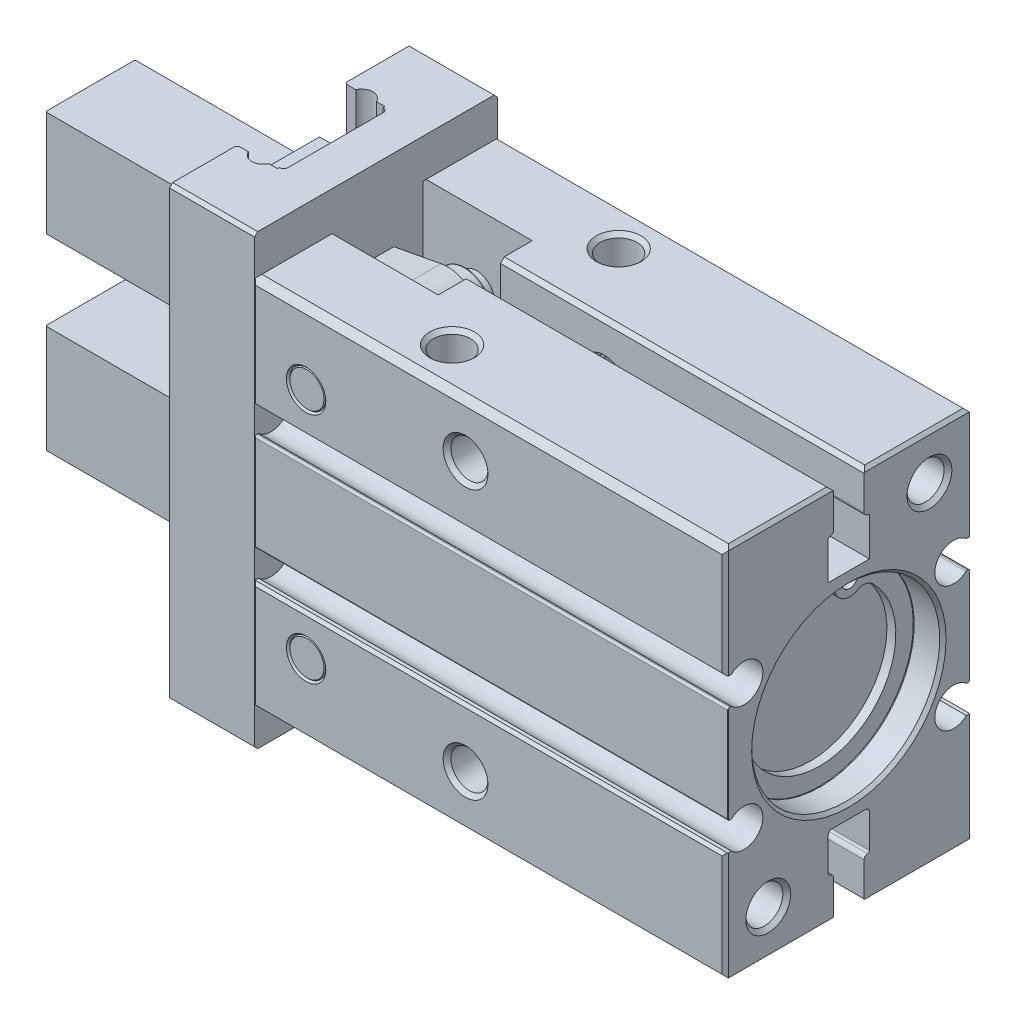
SolidWorks part; units mm, degrees
ref_plane "前视基准面" through (0, 0, 0) normal (0, 0, 1) x (1, 0, 0)
ref_plane "上视基准面" through (0, 0, 0) normal (0, 1, 0) x (1, 0, 0)
ref_plane "右视基准面" through (0, 0, 0) normal (1, 0, 0) x (0, 0, -1)
ref_plane "基准面1" through (0, 0, 0) normal (1, 0, 0) x (0, 0, -1)
sketch "草图1" plane through (0, 0, 0) normal (1, 0, 0) x (0, 0, -1)
  line L0 (-13.8, 20.2929) -> (-13.8, 8.85)
  line L1 (-13.8, 8.85) -> (-13.5, 8.55)
  line L2 (-13.5, 8.55) -> (-13.1169, 8.55)
  line L3 (-13.1925, 5.45) -> (-13.3, 5.45)
  line L4 (-13.5, 5.25) -> (-13.5, -5.25)
  line L5 (-13.3, -5.45) -> (-13.1925, -5.45)
  line L6 (-13.1169, -8.55) -> (-13.5, -8.55)
  line L7 (-13.5, -8.55) -> (-13.8, -8.85)
  line L8 (-13.8, -8.85) -> (-13.8, -20.2929)
  line L9 (-13.8, -20.2929) -> (-13.0929, -21)
  line L10 (-13.0929, -21) -> (-2.1243, -21)
  line L11 (-2.1243, -21) -> (-1.7, -20.5757)
  line L12 (-1.7, -20.5757) -> (-1.7, -16.8)
  line L13 (-2.3, -16.2) -> (-2.3, -12.4)
  line L14 (-1.9, -12) -> (1.9, -12)
  line L15 (2.3, -12.4) -> (2.3, -16.2)
  line L16 (1.7, -16.8) -> (1.7, -20.5757)
  line L17 (1.7, -20.5757) -> (2.1243, -21)
  line L18 (2.1243, -21) -> (13.0929, -21)
  line L19 (13.0929, -21) -> (13.8, -20.2929)
  line L20 (13.8, -20.2929) -> (13.8, -8.85)
  line L21 (13.8, -8.85) -> (13.5, -8.55)
  line L22 (13.5, -8.55) -> (13.1169, -8.55)
  line L23 (13.1925, -5.45) -> (13.3, -5.45)
  line L24 (13.5, -5.25) -> (13.5, 5.25)
  line L25 (13.3, 5.45) -> (13.1925, 5.45)
  line L26 (13.1169, 8.55) -> (13.5, 8.55)
  line L27 (13.5, 8.55) -> (13.8, 8.85)
  line L28 (13.8, 8.85) -> (13.8, 20.2929)
  line L29 (13.8, 20.2929) -> (13.0929, 21)
  line L30 (13.0929, 21) -> (2.1243, 21)
  line L31 (2.1243, 21) -> (1.7, 20.5757)
  line L32 (1.7, 20.5757) -> (1.7, 16.8)
  line L33 (2.3, 16.2) -> (2.3, 12)
  line L34 (2.3, 12) -> (-2.3, 12)
  line L35 (-2.3, 12) -> (-2.3, 16.2)
  line L36 (-1.7, 16.8) -> (-1.7, 20.5757)
  line L37 (-1.7, 20.5757) -> (-2.1243, 21)
  line L38 (-2.1243, 21) -> (-13.0929, 21)
  line L39 (-13.0929, 21) -> (-13.8, 20.2929)
  arc A0 (-13.1169, 8.55) -> (-13.0627, 5.4022) centre (-11.7, 7) cw
  arc A1 (-13.0627, 5.4022) -> (-13.1925, 5.45) centre (-13.1925, 5.25) ccw
  arc A2 (-13.3, 5.45) -> (-13.5, 5.25) centre (-13.3, 5.25) ccw
  arc A3 (-13.5, -5.25) -> (-13.3, -5.45) centre (-13.3, -5.25) ccw
  arc A4 (-13.1925, -5.45) -> (-13.0627, -5.4022) centre (-13.1925, -5.25) ccw
  arc A5 (-13.0627, -5.4022) -> (-13.1169, -8.55) centre (-11.7, -7) cw
  arc A6 (-1.7, -16.8) -> (-2.1, -16.4) centre (-2.1, -16.8) ccw
  arc A7 (-2.1, -16.4) -> (-2.3, -16.2) centre (-2.1, -16.2) cw
  arc A8 (-2.3, -12.4) -> (-1.9, -12) centre (-1.9, -12.4) cw
  arc A9 (1.9, -12) -> (2.3, -12.4) centre (1.9, -12.4) cw
  arc A10 (2.3, -16.2) -> (2.1, -16.4) centre (2.1, -16.2) cw
  arc A11 (2.1, -16.4) -> (1.7, -16.8) centre (2.1, -16.8) ccw
  arc A12 (13.1169, -8.55) -> (13.0627, -5.4022) centre (11.7, -7) cw
  arc A13 (13.0627, -5.4022) -> (13.1925, -5.45) centre (13.1925, -5.25) ccw
  arc A14 (13.3, -5.45) -> (13.5, -5.25) centre (13.3, -5.25) ccw
  arc A15 (13.5, 5.25) -> (13.3, 5.45) centre (13.3, 5.25) ccw
  arc A16 (13.1925, 5.45) -> (13.0627, 5.4022) centre (13.1925, 5.25) ccw
  arc A17 (13.0627, 5.4022) -> (13.1169, 8.55) centre (11.7, 7) cw
  arc A18 (1.7, 16.8) -> (2.1, 16.4) centre (2.1, 16.8) ccw
  arc A19 (2.1, 16.4) -> (2.3, 16.2) centre (2.1, 16.2) cw
  arc A20 (-2.3, 16.2) -> (-2.1, 16.4) centre (-2.1, 16.2) cw
  arc A21 (-2.1, 16.4) -> (-1.7, 16.8) centre (-2.1, 16.8) ccw
extrude "凸台-拉伸1" add sketch "草图1" against normal blind 52.8
ref_plane "基准面2" through (0, 0, 0) normal (0, 1, 0) x (1, 0, 0)
sketch "草图2" plane through (0, 0, 0) normal (0, 1, 0) x (1, 0, 0)
  line L0 (-52.8, 5.25) -> (-52.8, -5.25)
  line L1 (-52.8, -5.25) -> (-40.6, -5.25)
  line L2 (-40.6, -5.25) -> (-40.6, 5.25)
  line L3 (-40.6, 5.25) -> (-52.8, 5.25)
extrude "切除-拉伸1" cut sketch "草图2" against normal blind 21 and the other way blind 21
ref_plane "基准面3" through (-29, 0, 0) normal (1, 0, 0) x (0, 0, -1)
sketch "草图3" plane through (-29, 0, 0) normal (1, 0, 0) x (0, 0, -1)
  line L0 (-13.8, 15) -> (-13.8, 17.5)
  line L1 (-13.8, 17.5) -> (-13.367, 17.067)
  line L2 (-13.367, 17.067) -> (-3.8, 17.067)
  line L3 (-3.8, 17.067) -> (-3.8, 17.51)
  line L4 (-3.8, 17.51) -> (3.8, 17.51)
  line L5 (3.8, 17.51) -> (3.8, 17.067)
  line L6 (3.8, 17.067) -> (13.367, 17.067)
  line L7 (13.367, 17.067) -> (13.8, 17.5)
  line L8 (13.8, 17.5) -> (13.8, 15)
  line L9 (13.8, 15) -> (-13.8, 15)
  line L10 (13.8, 15) -> (-13.8, 15) construction
revolve "切除-旋转1" cut sketch "草图3" angle 360 about L10 reverse direction yes
ref_plane "基准面4" through (-29, 0, 0) normal (1, 0, 0) x (0, 0, -1)
sketch "草图4" plane through (-29, 0, 0) normal (1, 0, 0) x (0, 0, -1)
  line L0 (-13.8, -15) -> (-13.8, -12.5)
  line L1 (-13.8, -12.5) -> (-13.367, -12.933)
  line L2 (-13.367, -12.933) -> (-3.8, -12.933)
  line L3 (-3.8, -12.933) -> (-3.8, -12.49)
  line L4 (-3.8, -12.49) -> (3.8, -12.49)
  line L5 (3.8, -12.49) -> (3.8, -12.933)
  line L6 (3.8, -12.933) -> (13.367, -12.933)
  line L7 (13.367, -12.933) -> (13.8, -12.5)
  line L8 (13.8, -12.5) -> (13.8, -15)
  line L9 (13.8, -15) -> (-13.8, -15)
  line L10 (13.8, -15) -> (-13.8, -15) construction
revolve "切除-旋转2" cut sketch "草图4" angle 360 about L10 reverse direction yes
ref_plane "基准面5" through (0, 0, 0) normal (0, 1, 0) x (1, 0, 0)
sketch "草图5" plane through (0, 0, 0) normal (0, 1, 0) x (1, 0, 0)
  line L0 (-53.8, -14.8) -> (1, -14.8)
  line L1 (1, -14.8) -> (1, 14.8)
  line L2 (1, 14.8) -> (-53.8, 14.8)
  line L3 (-53.8, 14.8) -> (-53.8, -14.8)
  line L4 (-52.8, 13.4464) -> (-52.8, -13.4464)
  line L5 (-52.8, -13.4464) -> (-52.4464, -13.8)
  line L6 (-52.4464, -13.8) -> (-0.3536, -13.8)
  line L7 (-0.3536, -13.8) -> (0, -13.4464)
  line L8 (0, -13.4464) -> (0, 13.4464)
  line L9 (0, 13.4464) -> (-0.3536, 13.8)
  line L10 (-0.3536, 13.8) -> (-52.4464, 13.8)
  line L11 (-52.4464, 13.8) -> (-52.8, 13.4464)
extrude "切除-拉伸2" cut sketch "草图5" against normal blind 21 and the other way blind 21
ref_plane "基准面6" through (0, 0, 0) normal (0, 0, 1) x (1, 0, 0)
sketch "草图6" plane through (0, 0, 0) normal (0, 0, 1) x (1, 0, 0)
  line L0 (-53.8, 22) -> (-53.8, -22)
  line L1 (-53.8, -22) -> (1, -22)
  line L2 (1, -22) -> (1, 22)
  line L3 (1, 22) -> (-53.8, 22)
  line L4 (-52.8, -20.6464) -> (-52.4464, -21)
  line L5 (-52.4464, -21) -> (-0.3536, -21)
  line L6 (-0.3536, -21) -> (0, -20.6464)
  line L7 (0, -20.6464) -> (0, 20.6464)
  line L8 (0, 20.6464) -> (-0.3536, 21)
  line L9 (-0.3536, 21) -> (-52.4464, 21)
  line L10 (-52.4464, 21) -> (-52.8, 20.6464)
  line L11 (-52.8, 20.6464) -> (-52.8, -20.6464)
extrude "切除-拉伸3" cut sketch "草图6" against normal blind 13.8 and the other way blind 13.8
ref_plane "基准面7" through (-52.8, 0, 0) normal (1, 0, 0) x (0, 0, -1)
sketch "草图7" plane through (-52.8, 0, 0) normal (1, 0, 0) x (0, 0, -1)
  line L0 (-13.55, -24.6464) -> (-13.1964, -25)
  line L1 (-13.1964, -25) -> (13.1964, -25)
  line L2 (13.1964, -25) -> (13.55, -24.6464)
  line L3 (13.55, -24.6464) -> (13.55, 24.6464)
  line L4 (13.55, 24.6464) -> (13.1964, 25)
  line L5 (13.1964, 25) -> (-13.1964, 25)
  line L6 (-13.1964, 25) -> (-13.55, 24.6464)
  line L7 (-13.55, 24.6464) -> (-13.55, -24.6464)
extrude "凸台-拉伸2" add sketch "草图7" against normal blind 9.5
ref_plane "基准面8" through (0, 0, 0) normal (0, 1, 0) x (1, 0, 0)
sketch "草图8" plane through (0, 0, 0) normal (0, 1, 0) x (1, 0, 0)
  line L0 (-62.3, -6.2121) -> (-62.0879, -6)
  line L1 (-62.0879, -6) -> (-61.0456, -6)
  line L2 (-58.7544, -6) -> (-57.8, -6)
  line L3 (-57.8, -6) -> (-57.8, -5.8)
  line L4 (-57.3, -5.3) -> (-57.3, 5.3)
  line L5 (-57.8, 5.8) -> (-57.8, 6)
  line L6 (-57.8, 6) -> (-58.7544, 6)
  line L7 (-61.0456, 6) -> (-62.0879, 6)
  line L8 (-62.0879, 6) -> (-62.3, 6.2121)
  line L9 (-62.3, 6.2121) -> (-62.3, -6.2121)
  arc A0 (-61.0456, -6) -> (-58.7544, -6) centre (-59.9, -5.5) ccw
  arc A1 (-57.8, -5.8) -> (-57.3, -5.3) centre (-57.8, -5.3) ccw
  arc A2 (-57.3, 5.3) -> (-57.8, 5.8) centre (-57.8, 5.3) ccw
  arc A3 (-58.7544, 6) -> (-61.0456, 6) centre (-59.9, 5.5) ccw
extrude "切除-拉伸4" cut sketch "草图8" against normal blind 25 and the other way blind 25
ref_plane "基准面9" through (0, 0.01, 0) normal (0, 1, 0) x (1, 0, 0)
sketch "草图9" plane through (0, 0.01, 0) normal (0, 1, 0) x (1, 0, 0)
  line L0 (-64.1, -5) -> (-61.81, -5)
  line L1 (-61.81, -5) -> (-61.1136, -6.2007)
  line L2 (-58.6864, -6.2007) -> (-57.99, -5)
  line L3 (-57.99, -5) -> (-57.6414, -5)
  line L4 (-57.6414, -5) -> (-57.5, -4.8586)
  line L5 (-57.5, -4.8586) -> (-57.5, 4.8586)
  line L6 (-57.5, 4.8586) -> (-57.6414, 5)
  line L7 (-57.6414, 5) -> (-57.99, 5)
  line L8 (-57.99, 5) -> (-58.6864, 6.2007)
  line L9 (-61.1136, 6.2007) -> (-61.81, 5)
  line L10 (-61.81, 5) -> (-64.1, 5)
  line L11 (-64.1, 5) -> (-64.1, -5)
  arc A0 (-61.1136, -6.2007) -> (-58.6864, -6.2007) centre (-59.9, -6.5) ccw
  arc A1 (-58.6864, 6.2007) -> (-61.1136, 6.2007) centre (-59.9, 6.5) ccw
extrude "凸台-拉伸3" add sketch "草图9" along normal blind 19.4
ref_plane "基准面10" through (0, -0.01, 0) normal (0, 1, 0) x (1, 0, 0)
sketch "草图10" plane through (0, -0.01, 0) normal (0, 1, 0) x (1, 0, 0)
  line L0 (-64.1, -5) -> (-61.81, -5)
  line L1 (-61.81, -5) -> (-61.1136, -6.2007)
  line L2 (-58.6864, -6.2007) -> (-57.99, -5)
  line L3 (-57.99, -5) -> (-57.6414, -5)
  line L4 (-57.6414, -5) -> (-57.5, -4.8586)
  line L5 (-57.5, -4.8586) -> (-57.5, 4.8586)
  line L6 (-57.5, 4.8586) -> (-57.6414, 5)
  line L7 (-57.6414, 5) -> (-57.99, 5)
  line L8 (-57.99, 5) -> (-58.6864, 6.2007)
  line L9 (-61.1136, 6.2007) -> (-61.81, 5)
  line L10 (-61.81, 5) -> (-64.1, 5)
  line L11 (-64.1, 5) -> (-64.1, -5)
  arc A0 (-61.1136, -6.2007) -> (-58.6864, -6.2007) centre (-59.9, -6.5) ccw
  arc A1 (-58.6864, 6.2007) -> (-61.1136, 6.2007) centre (-59.9, 6.5) ccw
extrude "凸台-拉伸4" add sketch "草图10" against normal blind 19.4
ref_plane "基准面11" through (0, 8.15, 0) normal (0, 1, 0) x (1, 0, 0)
sketch "草图11" plane through (0, 8.15, 0) normal (0, 1, 0) x (1, 0, 0)
  line L0 (-84.7, -4.8586) -> (-84.5586, -5)
  line L1 (-84.5586, -5) -> (-64.1, -5)
  line L2 (-64.1, -5) -> (-64.1, 5)
  line L3 (-64.1, 5) -> (-84.5586, 5)
  line L4 (-84.5586, 5) -> (-84.7, 4.8586)
  line L5 (-84.7, 4.8586) -> (-84.7, -4.8586)
extrude "凸台-拉伸5" add sketch "草图11" along normal blind 8.3999 and the other way blind 3.3658
ref_plane "基准面12" through (0, -16.16, 0) normal (0, 1, 0) x (1, 0, 0)
sketch "草图12" plane through (0, -16.16, 0) normal (0, 1, 0) x (1, 0, 0)
  line L0 (-84.7, -4.8586) -> (-84.5586, -5)
  line L1 (-84.5586, -5) -> (-64.1, -5)
  line L2 (-64.1, -5) -> (-64.1, 5)
  line L3 (-64.1, 5) -> (-84.5586, 5)
  line L4 (-84.5586, 5) -> (-84.7, 4.8586)
  line L5 (-84.7, 4.8586) -> (-84.7, -4.8586)
extrude "凸台-拉伸6" add sketch "草图12" along normal blind 12 and the other way blind 0.0001
ref_plane "基准面13" through (-46.8, 0, 0) normal (1, 0, 0) x (0, 0, -1)
sketch "草图13" plane through (-46.8, 0, 0) normal (1, 0, 0) x (0, 0, -1)
  line L0 (-13.8, 13) -> (-13.8, 15)
  line L1 (-13.8, 15) -> (-4, 15)
  line L2 (-4, 15) -> (-4, 15.8)
  line L3 (-3.8, 16) -> (-2, 16)
  line L4 (-2, 16) -> (-2, 16.3)
  line L5 (-1.8, 16.5) -> (1.8, 16.5)
  line L6 (2, 16.3) -> (2, 16)
  line L7 (2, 16) -> (3.8, 16)
  line L8 (4, 15.8) -> (4, 15)
  line L9 (4, 15) -> (13.8, 15)
  line L10 (13.8, 15) -> (13.8, 13)
  line L11 (13.8, 13) -> (-13.8, 13)
  line L12 (13.8, 13) -> (-13.8, 13) construction
  arc A0 (-4, 15.8) -> (-3.8, 16) centre (-3.8, 15.8) cw
  arc A1 (-2, 16.3) -> (-1.8, 16.5) centre (-1.8, 16.3) cw
  arc A2 (1.8, 16.5) -> (2, 16.3) centre (1.8, 16.3) cw
  arc A3 (3.8, 16) -> (4, 15.8) centre (3.8, 15.8) cw
revolve "旋转1" add sketch "草图13" angle 360 about L12 reverse direction yes
ref_plane "基准面14" through (-46.8, 0, 0) normal (1, 0, 0) x (0, 0, -1)
sketch "草图14" plane through (-46.8, 0, 0) normal (1, 0, 0) x (0, 0, -1)
  line L0 (-13.8, -13) -> (-13.8, -11)
  line L1 (-13.8, -11) -> (-4, -11)
  line L2 (-4, -11) -> (-4, -10.2)
  line L3 (-3.8, -10) -> (-2, -10)
  line L4 (-2, -10) -> (-2, -9.7)
  line L5 (-1.8, -9.5) -> (1.8, -9.5)
  line L6 (2, -9.7) -> (2, -10)
  line L7 (2, -10) -> (3.8, -10)
  line L8 (4, -10.2) -> (4, -11)
  line L9 (4, -11) -> (13.8, -11)
  line L10 (13.8, -11) -> (13.8, -13)
  line L11 (13.8, -13) -> (-13.8, -13)
  line L12 (13.8, -13) -> (-13.8, -13) construction
  arc A0 (-4, -10.2) -> (-3.8, -10) centre (-3.8, -10.2) cw
  arc A1 (-2, -9.7) -> (-1.8, -9.5) centre (-1.8, -9.7) cw
  arc A2 (1.8, -9.5) -> (2, -9.7) centre (1.8, -9.7) cw
  arc A3 (3.8, -10) -> (4, -10.2) centre (3.8, -10.2) cw
revolve "旋转2" add sketch "草图14" angle 360 about L12 reverse direction yes
ref_plane "基准面15" through (-46.8, 0, 0) normal (1, 0, 0) x (0, 0, -1)
sketch "草图15" plane through (-46.8, 0, 0) normal (1, 0, 0) x (0, 0, -1)
  line L0 (13.7, 13) -> (13.7, 14.9)
  line L1 (13.7, 14.9) -> (13.6, 15)
  line L2 (13.6, 15) -> (13.8, 15.2)
  line L3 (13.8, 15.2) -> (13.8, 13)
  line L4 (13.8, 13) -> (13.7, 13)
  line L5 (13.8, 13) -> (13.7, 13) construction
revolve "切除-旋转3" cut sketch "草图15" angle 360 about L5 reverse direction yes
ref_plane "基准面16" through (-46.8, 0, 0) normal (1, 0, 0) x (0, 0, -1)
sketch "草图16" plane through (-46.8, 0, 0) normal (1, 0, 0) x (0, 0, -1)
  line L0 (-13.8, 13) -> (-13.8, 15.2)
  line L1 (-13.8, 15.2) -> (-13.6, 15)
  line L2 (-13.6, 15) -> (-13.7, 14.9)
  line L3 (-13.7, 14.9) -> (-13.7, 13)
  line L4 (-13.7, 13) -> (-13.8, 13)
  line L5 (-13.7, 13) -> (-13.8, 13) construction
revolve "切除-旋转4" cut sketch "草图16" angle 360 about L5 reverse direction yes
ref_plane "基准面17" through (-46.8, 0, 0) normal (1, 0, 0) x (0, 0, -1)
sketch "草图17" plane through (-46.8, 0, 0) normal (1, 0, 0) x (0, 0, -1)
  line L0 (13.7, -13) -> (13.7, -11.1)
  line L1 (13.7, -11.1) -> (13.6, -11)
  line L2 (13.6, -11) -> (13.8, -10.8)
  line L3 (13.8, -10.8) -> (13.8, -13)
  line L4 (13.8, -13) -> (13.7, -13)
  line L5 (13.8, -13) -> (13.7, -13) construction
revolve "切除-旋转5" cut sketch "草图17" angle 360 about L5 reverse direction yes
ref_plane "基准面18" through (-46.8, 0, 0) normal (1, 0, 0) x (0, 0, -1)
sketch "草图18" plane through (-46.8, 0, 0) normal (1, 0, 0) x (0, 0, -1)
  line L0 (-13.8, -13) -> (-13.8, -10.8)
  line L1 (-13.8, -10.8) -> (-13.6, -11)
  line L2 (-13.6, -11) -> (-13.7, -11.1)
  line L3 (-13.7, -11.1) -> (-13.7, -13)
  line L4 (-13.7, -13) -> (-13.8, -13)
  line L5 (-13.7, -13) -> (-13.8, -13) construction
revolve "切除-旋转6" cut sketch "草图18" angle 360 about L5 reverse direction yes
ref_plane "基准面19" through (0, 0, 0) normal (0, 0, 1) x (1, 0, 0)
sketch "草图19" plane through (0, 0, 0) normal (0, 0, 1) x (1, 0, 0)
  line L0 (-49.6, 0) -> (-49.6, 3.6464)
  line L1 (-49.6, 3.6464) -> (-49.2464, 4)
  line L2 (-49.2464, 4) -> (-41.7, 4)
  line L3 (-41.7, 4) -> (-40.7, 5)
  line L4 (-40.7, 5) -> (-40.59, 5)
  line L5 (-40.59, 5) -> (-40.59, 0)
  line L6 (-40.59, 0) -> (-49.6, 0)
  line L7 (-40.59, 0) -> (-49.6, 0) construction
revolve "旋转3" add sketch "草图19" angle 360 about L7 reverse direction yes
ref_plane "基准面20" through (0, 0, 0) normal (0, 0, 1) x (1, 0, 0)
sketch "草图20" plane through (0, 0, 0) normal (0, 0, 1) x (1, 0, 0)
  line L0 (-50.3, -4.5) -> (-43.3, -4.5)
  line L1 (-43.3, -4.5) -> (-43.3, 4.5)
  line L2 (-43.3, 4.5) -> (-50.3, 4.5)
  line L3 (-50.3, 4.5) -> (-50.3, -4.5)
extrude "切除-拉伸5" cut sketch "草图20" against normal blind 2.1 and the other way blind 2.1
ref_plane "基准面21" through (0, 0, 0) normal (0, 0, 1) x (1, 0, 0)
sketch "草图21" plane through (0, 0, 0) normal (0, 0, 1) x (1, 0, 0)
  line L0 (-60.9083, -12.6462) -> (-60.8874, -13.846)
  line L1 (-59.8701, -14.8284) -> (-58.8502, -14.8106)
  line L2 (-58.8502, -14.8106) -> (-47.5371, -16.9315)
  line L3 (-42.8708, -12.2507) -> (-43.3, -10)
  line L4 (-43.3, -10) -> (-43.3, 10)
  line L5 (-43.3, 10) -> (-42.8708, 12.2507)
  line L6 (-47.5371, 16.9315) -> (-58.8502, 14.8106)
  line L7 (-58.8502, 14.8106) -> (-59.8701, 14.8284)
  line L8 (-60.8874, 13.846) -> (-60.9083, 12.6462)
  line L9 (-59.9259, 11.6289) -> (-58.9061, 11.6111)
  line L10 (-58.9061, 11.6111) -> (-51.8631, 10.0344)
  line L11 (-50.3, 8.0827) -> (-50.3, -8.0827)
  line L12 (-51.8631, -10.0344) -> (-58.9061, -11.6111)
  line L13 (-58.9061, -11.6111) -> (-59.9259, -11.6289)
  arc A0 (-59.9259, -11.6289) -> (-60.9083, -12.6462) centre (-59.9085, -12.6287) ccw
  arc A1 (-60.8874, -13.846) -> (-59.8701, -14.8284) centre (-59.8875, -13.8285) ccw
  arc A2 (-47.5371, -16.9315) -> (-42.8708, -12.2507) centre (-46.8, -13) ccw
  arc A3 (-42.8708, 12.2507) -> (-47.5371, 16.9315) centre (-46.8, 13) ccw
  arc A4 (-59.8701, 14.8284) -> (-60.8874, 13.846) centre (-59.8875, 13.8285) ccw
  arc A5 (-60.9083, 12.6462) -> (-59.9259, 11.6289) centre (-59.9085, 12.6287) ccw
  arc A6 (-51.8631, 10.0344) -> (-50.3, 8.0827) centre (-52.3, 8.0827) cw
  arc A7 (-50.3, -8.0827) -> (-51.8631, -10.0344) centre (-52.3, -8.0827) cw
extrude "凸台-拉伸7" add sketch "草图21" against normal blind 2 and the other way blind 2
ref_plane "基准面22" through (0, 0, 0) normal (0, 0, 1) x (1, 0, 0)
sketch "草图22" plane through (0, 0, 0) normal (0, 0, 1) x (1, 0, 0)
  line L0 (-79.7, 8.15) -> (-81.7, 8.15)
  line L1 (-81.7, 8.15) -> (-81.321, 8.529)
  line L2 (-81.321, 8.529) -> (-81.321, 15.781)
  line L3 (-81.321, 15.781) -> (-81.7, 16.16)
  line L4 (-81.7, 16.16) -> (-79.7, 16.16)
  line L5 (-79.7, 16.16) -> (-79.7, 8.15)
  line L6 (-79.7, 16.16) -> (-79.7, 8.15) construction
revolve "切除-旋转7" cut sketch "草图22" angle 360 about L6 reverse direction yes
ref_plane "基准面23" through (0, 0, 0) normal (0, 0, 1) x (1, 0, 0)
sketch "草图23" plane through (0, 0, 0) normal (0, 0, 1) x (1, 0, 0)
  line L0 (-79.7, -16.16) -> (-81.7, -16.16)
  line L1 (-81.7, -16.16) -> (-81.321, -15.781)
  line L2 (-81.321, -15.781) -> (-81.321, -8.529)
  line L3 (-81.321, -8.529) -> (-81.7, -8.15)
  line L4 (-81.7, -8.15) -> (-79.7, -8.15)
  line L5 (-79.7, -8.15) -> (-79.7, -16.16)
  line L6 (-79.7, -8.15) -> (-79.7, -16.16) construction
revolve "切除-旋转8" cut sketch "草图23" angle 360 about L6 reverse direction yes
ref_plane "基准面24" through (0, 0, 0) normal (0, 0, 1) x (1, 0, 0)
sketch "草图24" plane through (0, 0, 0) normal (0, 0, 1) x (1, 0, 0)
  line L0 (-70.7, 8.15) -> (-72.7, 8.15)
  line L1 (-72.7, 8.15) -> (-72.321, 8.529)
  line L2 (-72.321, 8.529) -> (-72.321, 15.781)
  line L3 (-72.321, 15.781) -> (-72.7, 16.16)
  line L4 (-72.7, 16.16) -> (-70.7, 16.16)
  line L5 (-70.7, 16.16) -> (-70.7, 8.15)
  line L6 (-70.7, 16.16) -> (-70.7, 8.15) construction
revolve "切除-旋转9" cut sketch "草图24" angle 360 about L6 reverse direction yes
ref_plane "基准面25" through (0, 0, 0) normal (0, 0, 1) x (1, 0, 0)
sketch "草图25" plane through (0, 0, 0) normal (0, 0, 1) x (1, 0, 0)
  line L0 (-70.7, -16.16) -> (-72.7, -16.16)
  line L1 (-72.7, -16.16) -> (-72.321, -15.781)
  line L2 (-72.321, -15.781) -> (-72.321, -8.529)
  line L3 (-72.321, -8.529) -> (-72.7, -8.15)
  line L4 (-72.7, -8.15) -> (-70.7, -8.15)
  line L5 (-70.7, -8.15) -> (-70.7, -16.16)
  line L6 (-70.7, -8.15) -> (-70.7, -16.16) construction
revolve "切除-旋转10" cut sketch "草图25" angle 360 about L6 reverse direction yes
ref_plane "基准面26" through (0, -19.41, 0) normal (0, 1, 0) x (1, 0, 0)
sketch "草图26" plane through (0, -19.41, 0) normal (0, 1, 0) x (1, 0, 0)
  circle A0 centre (-61, -2.25) radius 1.65
  circle A1 centre (-61, -2.25) radius 1.5
extrude "切除-拉伸6" cut sketch "草图26" along normal blind 0.2
ref_plane "基准面27" through (0, -19.41, 0) normal (0, 1, 0) x (1, 0, 0)
sketch "草图27" plane through (0, -19.41, 0) normal (0, 1, 0) x (1, 0, 0)
  line L0 (-62, -2.5) -> (-61.25, -2.5)
  line L1 (-61.25, -2.5) -> (-61.25, -3.25)
  line L2 (-61.25, -3.25) -> (-60.75, -3.25)
  line L3 (-60.75, -3.25) -> (-60.75, -2.5)
  line L4 (-60.75, -2.5) -> (-60, -2.5)
  line L5 (-60, -2.5) -> (-60, -2)
  line L6 (-60, -2) -> (-60.75, -2)
  line L7 (-60.75, -2) -> (-60.75, -1.25)
  line L8 (-60.75, -1.25) -> (-61.25, -1.25)
  line L9 (-61.25, -1.25) -> (-61.25, -2)
  line L10 (-61.25, -2) -> (-62, -2)
  line L11 (-62, -2) -> (-62, -2.5)
extrude "切除-拉伸7" cut sketch "草图27" along normal blind 0.5
ref_plane "基准面28" through (0, -19.41, 0) normal (0, 1, 0) x (1, 0, 0)
sketch "草图28" plane through (0, -19.41, 0) normal (0, 1, 0) x (1, 0, 0)
  circle A0 centre (-61, 2.25) radius 1.65
  circle A1 centre (-61, 2.25) radius 1.5
extrude "凸台-拉伸8" add sketch "草图28" against normal blind 0.2
ref_plane "基准面29" through (0, -19.41, 0) normal (0, 1, 0) x (1, 0, 0)
sketch "草图29" plane through (0, -19.41, 0) normal (0, 1, 0) x (1, 0, 0)
  line L0 (-62, 2) -> (-61.25, 2)
  line L1 (-61.25, 2) -> (-61.25, 1.25)
  line L2 (-61.25, 1.25) -> (-60.75, 1.25)
  line L3 (-60.75, 1.25) -> (-60.75, 2)
  line L4 (-60.75, 2) -> (-60, 2)
  line L5 (-60, 2) -> (-60, 2.5)
  line L6 (-60, 2.5) -> (-60.75, 2.5)
  line L7 (-60.75, 2.5) -> (-60.75, 3.25)
  line L8 (-60.75, 3.25) -> (-61.25, 3.25)
  line L9 (-61.25, 3.25) -> (-61.25, 2.5)
  line L10 (-61.25, 2.5) -> (-62, 2.5)
  line L11 (-62, 2.5) -> (-62, 2)
extrude "切除-拉伸8" cut sketch "草图29" along normal blind 0.5
ref_plane "基准面30" through (0, 19.41, 0) normal (0, 1, 0) x (1, 0, 0)
sketch "草图30" plane through (0, 19.41, 0) normal (0, 1, 0) x (1, 0, 0)
  circle A0 centre (-61, -2.25) radius 1.65
  circle A1 centre (-61, -2.25) radius 1.5
extrude "切除-拉伸9" cut sketch "草图30" against normal blind 0.2
ref_plane "基准面31" through (0, 19.41, 0) normal (0, 1, 0) x (1, 0, 0)
sketch "草图31" plane through (0, 19.41, 0) normal (0, 1, 0) x (1, 0, 0)
  line L0 (-62, -2.5) -> (-61.25, -2.5)
  line L1 (-61.25, -2.5) -> (-61.25, -3.25)
  line L2 (-61.25, -3.25) -> (-60.75, -3.25)
  line L3 (-60.75, -3.25) -> (-60.75, -2.5)
  line L4 (-60.75, -2.5) -> (-60, -2.5)
  line L5 (-60, -2.5) -> (-60, -2)
  line L6 (-60, -2) -> (-60.75, -2)
  line L7 (-60.75, -2) -> (-60.75, -1.25)
  line L8 (-60.75, -1.25) -> (-61.25, -1.25)
  line L9 (-61.25, -1.25) -> (-61.25, -2)
  line L10 (-61.25, -2) -> (-62, -2)
  line L11 (-62, -2) -> (-62, -2.5)
extrude "切除-拉伸10" cut sketch "草图31" against normal blind 0.5
ref_plane "基准面32" through (0, 19.41, 0) normal (0, 1, 0) x (1, 0, 0)
sketch "草图32" plane through (0, 19.41, 0) normal (0, 1, 0) x (1, 0, 0)
  circle A0 centre (-61, 2.25) radius 1.65
  circle A1 centre (-61, 2.25) radius 1.5
extrude "切除-拉伸11" cut sketch "草图32" against normal blind 0.2
ref_plane "基准面33" through (0, 19.41, 0) normal (0, 1, 0) x (1, 0, 0)
sketch "草图33" plane through (0, 19.41, 0) normal (0, 1, 0) x (1, 0, 0)
  line L0 (-62, 2) -> (-61.25, 2)
  line L1 (-61.25, 2) -> (-61.25, 1.25)
  line L2 (-61.25, 1.25) -> (-60.75, 1.25)
  line L3 (-60.75, 1.25) -> (-60.75, 2)
  line L4 (-60.75, 2) -> (-60, 2)
  line L5 (-60, 2) -> (-60, 2.5)
  line L6 (-60, 2.5) -> (-60.75, 2.5)
  line L7 (-60.75, 2.5) -> (-60.75, 3.25)
  line L8 (-60.75, 3.25) -> (-61.25, 3.25)
  line L9 (-61.25, 3.25) -> (-61.25, 2.5)
  line L10 (-61.25, 2.5) -> (-62, 2.5)
  line L11 (-62, 2.5) -> (-62, 2)
extrude "切除-拉伸12" cut sketch "草图33" against normal blind 0.5
ref_plane "基准面34" through (0, 0, 7.5) normal (0, 0, 1) x (1, 0, 0)
sketch "草图34" plane through (0, 0, 7.5) normal (0, 0, 1) x (1, 0, 0)
  line L0 (-23, -14) -> (-22.75, -14)
  line L1 (-22.75, -14) -> (-22.75, -16)
  line L2 (-22.75, -16) -> (-20.933, -16)
  line L3 (-20.933, -16) -> (-20.933, -20.567)
  line L4 (-20.933, -20.567) -> (-20.5, -21)
  line L5 (-20.5, -21) -> (-23, -21)
  line L6 (-23, -21) -> (-23, -14)
  line L7 (-23, -21) -> (-23, -14) construction
revolve "切除-旋转11" cut sketch "草图34" angle 360 about L7 reverse direction yes
ref_plane "基准面35" through (0, 0, -7.5) normal (0, 0, 1) x (1, 0, 0)
sketch "草图35" plane through (0, 0, -7.5) normal (0, 0, 1) x (1, 0, 0)
  line L0 (-9.7, -14) -> (-9.45, -14)
  line L1 (-9.45, -14) -> (-9.45, -16)
  line L2 (-9.45, -16) -> (-7.633, -16)
  line L3 (-7.633, -16) -> (-7.633, -20.567)
  line L4 (-7.633, -20.567) -> (-7.2, -21)
  line L5 (-7.2, -21) -> (-9.7, -21)
  line L6 (-9.7, -21) -> (-9.7, -14)
  line L7 (-9.7, -21) -> (-9.7, -14) construction
revolve "切除-旋转12" cut sketch "草图35" angle 360 about L7 reverse direction yes
ref_plane "基准面36" through (-35, 0, 0) normal (1, 0, 0) x (0, 0, -1)
sketch "草图36" plane through (-35, 0, 0) normal (1, 0, 0) x (0, 0, -1)
  line L0 (-9.3, 12) -> (-10.501, 12)
  line L1 (-10.501, 12) -> (-11.367, 12.5)
  line L2 (-11.367, 12.5) -> (-11.367, 20.567)
  line L3 (-11.367, 20.567) -> (-11.8, 21)
  line L4 (-11.8, 21) -> (-9.3, 21)
  line L5 (-9.3, 21) -> (-9.3, 12)
  line L6 (-9.3, 21) -> (-9.3, 12) construction
revolve "切除-旋转13" cut sketch "草图36" angle 360 about L6 reverse direction yes
ref_plane "基准面37" through (-35, 0, 0) normal (1, 0, 0) x (0, 0, -1)
sketch "草图37" plane through (-35, 0, 0) normal (1, 0, 0) x (0, 0, -1)
  line L0 (9.3, 12) -> (8.099, 12)
  line L1 (8.099, 12) -> (7.233, 12.5)
  line L2 (7.233, 12.5) -> (7.233, 20.567)
  line L3 (7.233, 20.567) -> (6.8, 21)
  line L4 (6.8, 21) -> (9.3, 21)
  line L5 (9.3, 21) -> (9.3, 12)
  line L6 (9.3, 21) -> (9.3, 12) construction
revolve "切除-旋转14" cut sketch "草图37" angle 360 about L6 reverse direction yes
ref_plane "基准面38" through (0, 0, 0) normal (0, 0, 1) x (1, 0, 0)
sketch "草图38" plane through (0, 0, 0) normal (0, 0, 1) x (1, 0, 0)
  line L0 (-4.3, 0) -> (-4.3, 11)
  line L1 (-4.3, 11) -> (-3.2, 11)
  line L2 (-3.2, 11) -> (-3.2, 10.5)
  line L3 (-3.2, 10.5) -> (-0.3536, 10.5)
  line L4 (-0.3536, 10.5) -> (0, 10.8536)
  line L5 (0, 10.8536) -> (0, 0)
  line L6 (0, 0) -> (-4.3, 0)
  line L7 (0, 0) -> (-4.3, 0) construction
revolve "切除-旋转15" cut sketch "草图38" angle 360 about L7 reverse direction yes
ref_plane "基准面39" through (-4.3, 0, 0) normal (1, 0, 0) x (0, 0, -1)
sketch "草图39" plane through (-4.3, 0, 0) normal (1, 0, 0) x (0, 0, -1)
  line L0 (1.9838, 9.372) -> (1.7352, 8.1977)
  line L1 (-1.5307, 8.1945) -> (-1.759, 9.4168)
  arc A0 (-2.864, 10.1018) -> (3.1049, 10.0304) centre (0, 0) ccw
  arc A1 (3.1049, 10.0304) -> (1.9838, 9.372) centre (2.8447, 9.1898) ccw
  arc A2 (1.7352, 8.1977) -> (4.2133, 6.3537) centre (3.3984, 7.8456) ccw
  arc A3 (4.2133, 6.3537) -> (5.9818, 6.109) centre (4.9324, 5.0373) cw
  arc A4 (5.9818, 6.109) -> (-6.1592, 5.9302) centre (0, 0) cw
  arc A5 (-6.1592, 5.9302) -> (-4.3373, 6.1938) centre (-5.0786, 4.8898) cw
  arc A6 (-4.3373, 6.1938) -> (-1.5307, 8.1945) centre (-3.3984, 7.8456) ccw
  arc A7 (-1.759, 9.4168) -> (-2.864, 10.1018) centre (-2.624, 9.2552) ccw
  circle A8 centre (3.3984, 7.8456) radius 0.9
  circle A9 centre (-3.3984, 7.8456) radius 0.9
extrude "凸台-拉伸9" add sketch "草图39" along normal blind 1
ref_plane "基准面40" through (0, 0, 9) normal (0, 0, 1) x (1, 0, 0)
sketch "草图40" plane through (0, 0, 9) normal (0, 0, 1) x (1, 0, 0)
  line L0 (-11, -16) -> (-11, -14.799)
  line L1 (-11, -14.799) -> (-10.5, -13.933)
  line L2 (-10.5, -13.933) -> (-0.433, -13.933)
  line L3 (-0.433, -13.933) -> (0, -13.5)
  line L4 (0, -13.5) -> (0, -16)
  line L5 (0, -16) -> (-11, -16)
  line L6 (0, -16) -> (-11, -16) construction
revolve "切除-旋转16" cut sketch "草图40" angle 360 about L6 reverse direction yes
ref_plane "基准面41" through (0, 0, -9) normal (0, 0, 1) x (1, 0, 0)
sketch "草图41" plane through (0, 0, -9) normal (0, 0, 1) x (1, 0, 0)
  line L0 (-11, 16) -> (-11, 17.201)
  line L1 (-11, 17.201) -> (-10.5, 18.067)
  line L2 (-10.5, 18.067) -> (-0.433, 18.067)
  line L3 (-0.433, 18.067) -> (0, 18.5)
  line L4 (0, 18.5) -> (0, 16)
  line L5 (0, 16) -> (-11, 16)
  line L6 (0, 16) -> (-11, 16) construction
revolve "切除-旋转17" cut sketch "草图41" angle 360 about L6 reverse direction yes
